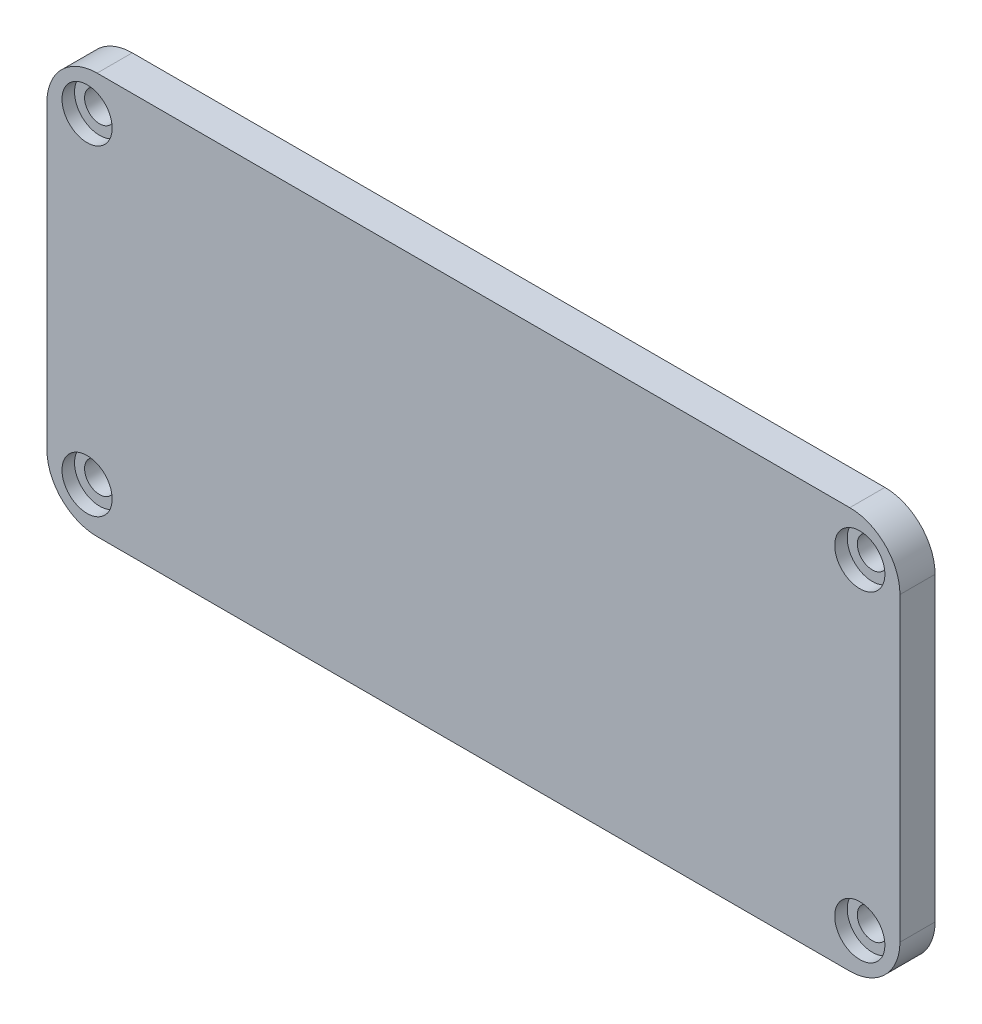
SolidWorks part; units mm, degrees
ref_plane "前视基准面" through (0, 0, 0) normal (0, 0, 1) x (1, 0, 0)
ref_plane "上视基准面" through (0, 0, 0) normal (0, 1, 0) x (1, 0, 0)
ref_plane "右视基准面" through (0, 0, 0) normal (1, 0, 0) x (0, 0, -1)
sketch "草图1" plane through (0, 0, 0) normal (0, 0, 1) x (1, 0, 0)
  line L1 (-72.5741, 35.4874) -> (77.4259, 35.4874)
  line L2 (-82.5741, 25.4874) -> (-82.5741, -34.5126)
  line L3 (-72.5741, -44.5126) -> (77.4259, -44.5126)
  line L4 (87.4259, 25.4874) -> (87.4259, -34.5126)
  arc A0 (-72.5741, 35.4874) -> (-82.5741, 25.4874) centre (-72.5741, 25.4874) ccw
  arc A1 (-72.5741, -44.5126) -> (-82.5741, -34.5126) centre (-72.5741, -34.5126) cw
  arc A2 (87.4259, 25.4874) -> (77.4259, 35.4874) centre (77.4259, 25.4874) ccw
  arc A3 (87.4259, -34.5126) -> (77.4259, -44.5126) centre (77.4259, -34.5126) cw
  dimension "D1" = 10
  dimension "D2" = 10
  dimension "D3" = 10
  dimension "D4" = 10
  dimension "D5" = 80
  dimension "D6" = 170
extrude "凸台-拉伸1" add sketch "草图1" along normal blind 7
ref_plane "for screw hole" through (0, 0, 7) normal (0, 0, 1) x (1, 0, 0)
sketch "草图2" plane through (0, 0, 7) normal (0, 0, 1) x (1, 0, 0)
  line L0 (77.4259, 35.4874) -> (-72.5741, 35.4874) construction
  line L1 (-82.5741, 25.4874) -> (-82.5741, -34.5126) construction
  line L2 (-72.5741, -44.5126) -> (77.4259, -44.5126) construction
  line L3 (87.4259, -34.5126) -> (87.4259, 25.4874) construction
  circle A0 centre (-74.5741, 27.4874) radius 3
  circle A1 centre (-74.5741, -36.5126) radius 3
  circle A2 centre (79.4259, 27.4874) radius 3
  circle A3 centre (79.4259, -36.5126) radius 3
  dimension "D2" = 6
  dimension "D3" = 6
  dimension "D4" = 6
  dimension "D8" = 8
  dimension "D9" = 8
  dimension "D10" = 8
  dimension "D11" = 6
  dimension "D5" = 8
  dimension "D6" = 8
  dimension "D7" = 8
  dimension "D12" = 8
  dimension "D13" = 8
extrude "切除-拉伸1" cut sketch "草图2" against normal blind 10 and the other way blind 39
ref_plane "for outer screw hole" through (0, 0, 7) normal (0, 0, 1) x (1, 0, 0)
sketch "草图3" plane through (0, 0, 7) normal (0, 0, 1) x (1, 0, 0)
  circle A0 centre (-74.5741, 27.4874) radius 5
  circle A1 centre (79.4259, 27.4874) radius 5
  circle A2 centre (79.4259, -36.5126) radius 5
  circle A3 centre (-74.5741, -36.5126) radius 5
  dimension "D1" = 10
  dimension "D2" = 10
  dimension "D3" = 10
  dimension "D4" = 10
extrude "切除-拉伸2" cut sketch "草图3" against normal blind 2.5
ref_plane "for stands" through (0, 0, 7) normal (0, 0, 1) x (1, 0, 0)
